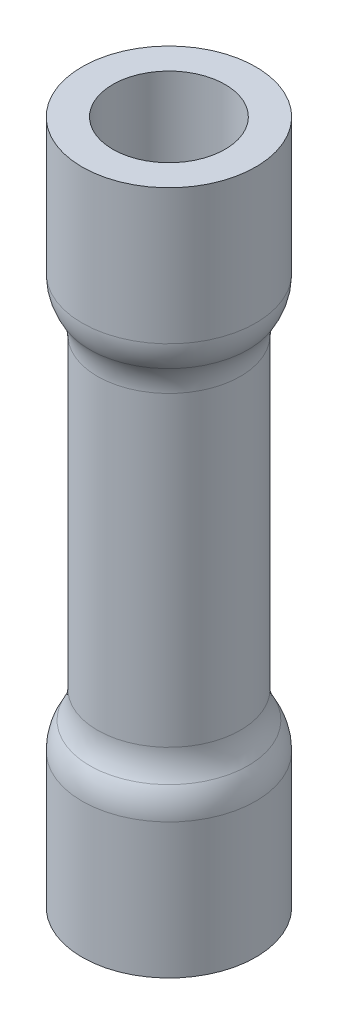
SolidWorks part; units mm, degrees
note: '?' marks a value the reader was unsure of.
material "PVC 0.007 Plasticized"
ref_plane "Front Plane" through (0, 0, 0) normal (0, 0, 1) x (1, 0, 0)
ref_plane "Top Plane" through (0, 0, 0) normal (0, 1, 0) x (1, 0, 0)
ref_plane "Right Plane" through (0, 0, 0) normal (1, 0, 0) x (0, 0, -1)
sketch "Sketch1" plane through (0, 0, 0) normal (0, 0, 1) x (1, 0, 0)
  line L0 (1.778, 12.319) -> (1.778, 4.699)
  line L1 (2.159, 0) -> (2.159, 3.361)
  line L2 (0, 8.509) -> (2.159, 8.509) construction
  line L3 (2.159, 13.657) -> (2.159, 17.018)
  line L5 (0, 17.018) -> (0, 0) construction
  arc A0 (2.159, 3.361) -> (1.9685, 4.03) centre (0.889, 3.361) ccw
  arc A1 (1.9685, 4.03) -> (1.778, 4.699) centre (3.048, 4.699) cw
  arc A2 (2.159, 13.657) -> (1.9685, 12.988) centre (0.889, 13.657) cw
  arc A3 (1.9685, 12.988) -> (1.778, 12.319) centre (3.048, 12.319) ccw
  dimension "D5" = 1.27
  dimension "D1" = 17.018
  dimension "D2" = 2.159
  dimension "D3" = 0.381
  dimension "D4" = 7.62
revolve "Revolve-Thin1" add sketch "Sketch1" angle 360 about L5
other "CPoint1" parameters "Diameter"=3.048, "StubLength"=6.858
ref_axis "Axis1" through (0, 27.018, 0) along (0, -1, 0)?
